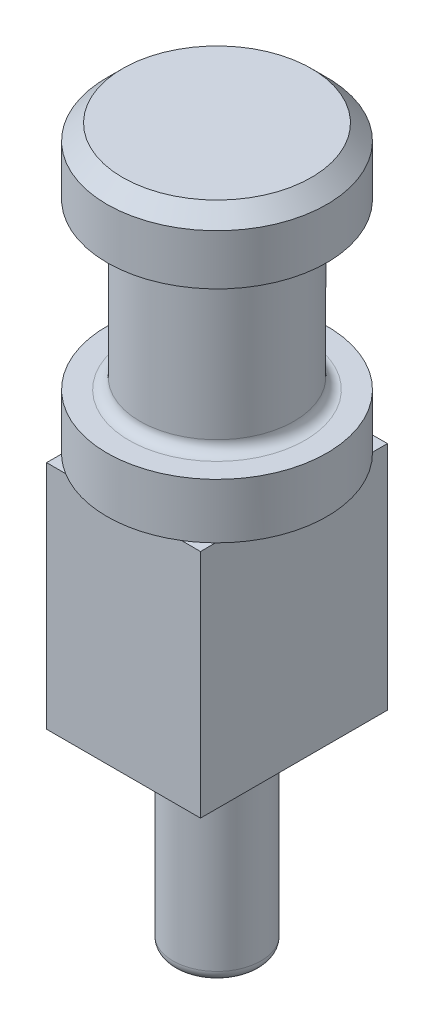
SolidWorks part; units mm, degrees
ref_plane "Front Plane" through (0, 0, 0) normal (0, 0, 1) x (1, 0, 0)
ref_plane "Top Plane" through (0, 0, 0) normal (0, 1, 0) x (1, 0, 0)
ref_plane "Right Plane" through (0, 0, 0) normal (1, 0, 0) x (0, 0, -1)
sketch "Sketch1" plane through (0, 0, 0) normal (0, 0, 1) x (1, 0, 0)
  line L0 (0, 45.9546) -> (0, -45.9546) construction
  line L1 (0, 45.9546) -> (8.5858, 45.9546)
  line L2 (8.5858, 45.9546) -> (10, 44.5404)
  line L3 (10, 44.5404) -> (10, 39.9546)
  line L4 (10, 39.9546) -> (7, 39.9546)
  line L5 (7, 39.9546) -> (7, 24.9546)
  line L6 (7, 24.9546) -> (10, 24.9546)
  line L7 (10, 24.9546) -> (10, 19.9546)
  line L8 (10, 19.9546) -> (7, 19.9546)
  line L9 (7, 19.9546) -> (7, -1.0454)
  line L10 (7, -1.0454) -> (4, -1.0454)
  line L11 (4, -1.0454) -> (4, -19.0454)
  line L12 (4, -19.0454) -> (0, -19.0454)
  line L13 (0, 45.9546) -> (0, -19.0454)
  point P15 (0, 23.0232)
  point P16 (0, 44.0259)
  point P17 (0, 33.6706)
  point P18 (0, 6.7274)
  point P19 (0, -22.0068)
  dimension "D1" = 2
  dimension "D2" = 10
  dimension "D3" = 7
  dimension "D4" = 225
  dimension "D5" = 15
  dimension "D6" = 10
  dimension "D7" = 5
  dimension "D8" = 21
  dimension "D9" = 39
  dimension "7" = 7
  dimension "D10" = 18
  dimension "D11" = 4
revolve "Revolve1" add sketch "Sketch1" angle 360 about L0
fillet "Fillet1" radius 1 1 edges at (0, -19.0454, 4)
cosmetic thread "Cosmetic Thread1" parameters "D1"=15, "D2"=6.619
fillet "Fillet2" radius 1 2 edges at (0, 24.9546, 7) (0, 39.9546, 7)
ref_plane "Plane1" through (0, 0, 8.5) normal (0, 0, 1) x (1, 0, 0)
sketch "Sketch2" plane through (0, 0, 8.5) normal (0, 0, 1) x (1, 0, 0)
  line L0 (7, 19.9546) -> (7, -1.0454)
  line L1 (-10, 19.9546) -> (10, 19.9546) construction
  line L2 (7, -1.0454) -> (-7, -1.0454)
  line L3 (-7, -1.0454) -> (-7, 19.9546)
  line L4 (-7, 19.9546) -> (7, 19.9546)
  line L5 (0, 19.9546) -> (0, -1.0454) construction
  dimension "D1" = 14
  dimension "D2" = 3
extrude "Boss-Extrude1" add sketch "Sketch2" against normal blind 17
